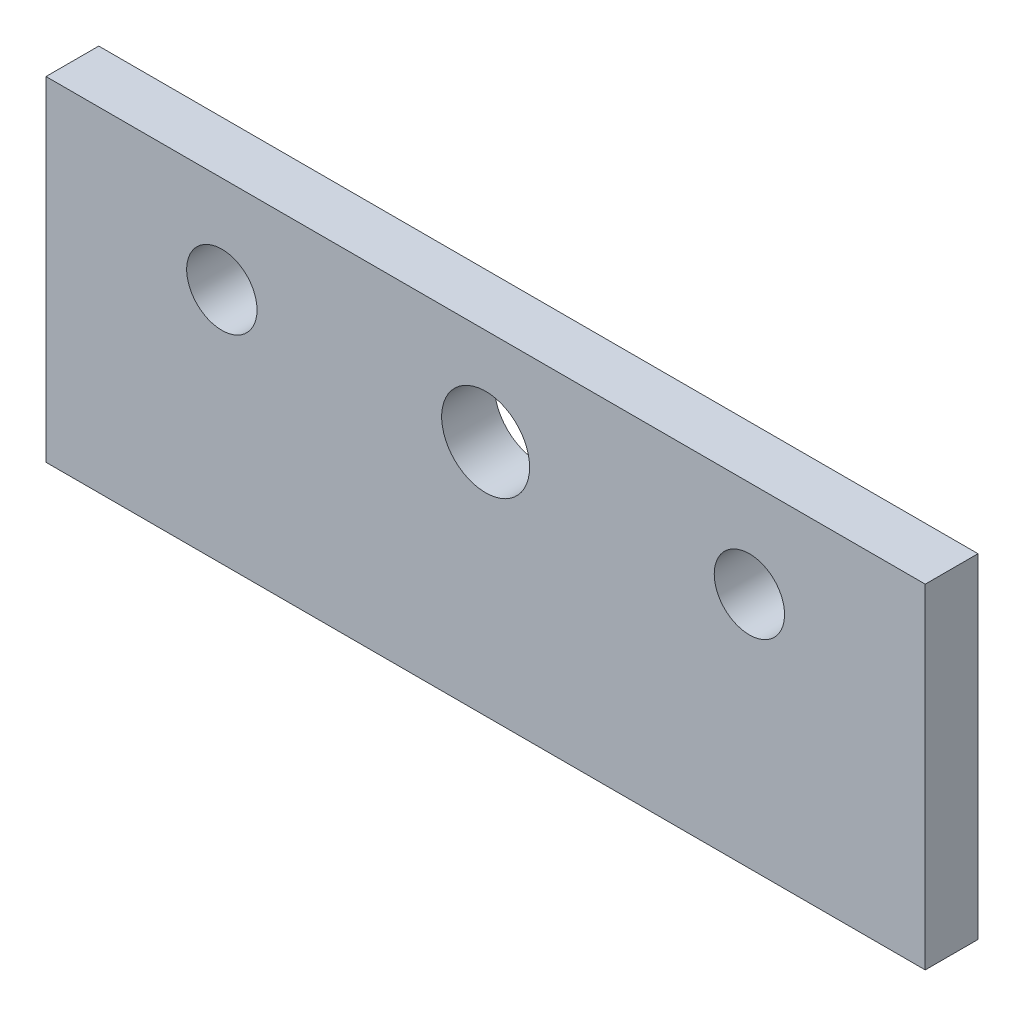
SolidWorks part; units mm, degrees
ref_plane "前视" through (0, 0, 0) normal (0, 0, 1) x (1, 0, 0)
ref_plane "上视" through (0, 0, 0) normal (0, 1, 0) x (1, 0, 0)
ref_plane "右视" through (0, 0, 0) normal (1, 0, 0) x (0, 0, -1)
sketch "草图1" plane through (0, 0, 0) normal (0, 0, 1) x (1, 0, 0)
  line L0 (-25, 4) -> (25, 4) construction
  line L1 (-25, 9.5) -> (25, 9.5)
  line L2 (-25, 9.5) -> (-25, -9.5)
  line L3 (-25, -9.5) -> (25, -9.5)
  line L4 (25, 9.5) -> (25, -9.5)
  line L5 (-25, 9.5) -> (25, -9.5) construction
  line L6 (-25, -9.5) -> (25, 9.5) construction
  line L7 (0, 0) -> (0, 15.22) construction
  circle A0 centre (-15, 4) radius 2
  circle A1 centre (15, 4) radius 2
  point P0 (0, 0)
  dimension "D4" = 4
  dimension "D1" = 50
  dimension "D2" = 19
  dimension "D3" = 5.5
  dimension "D5" = 30
base flange "基体-法兰1" sketch "草图1" thickness 3 reverse thickness direction no parameters "D1"=0.5
hole_wizard "M6 螺纹孔1" positions "草图8" profile "草图7" tap size "M6" standard "GB" end condition up to next
sketch "草图8" plane through (0, 0, 0) normal (0, 0, 1) x (1, 0, 0)
  line L0 (-15, 4) -> (15, 4) construction
  point P0 (0, 4)
sketch "草图7" plane through (0, 4, 0) normal (1, 0, 0) x (0, -1, 0)
  line L0 (0, 0) -> (0, 3)
  line L1 (0, 3) -> (2.5, 3)
  line L2 (2.5, 3) -> (2.5, 0)
  line L5 (2.5, 0) -> (0, 0)
  line L11 (0, -6.35) -> (0, 107.95) construction
  dimension "通孔螺纹孔钻头直径" = 5
  dimension "通孔螺纹孔钻头深度" = 3
cosmetic thread "孔螺蚊线1"
sketch "折弯-线1" plane through (0, 0, 0) normal (0, 1, 0) x (1, 0, 0)
sketch "边界框1" plane through (0, 0, 0) normal (0, 1, 0) x (1, 0, 0)
sheet metal parameters "钣金1" thickness 3 parameters "D1"=0.5
flat pattern "平板型式1" [suppressed]
sketch "折弯-线2" plane through (0, 0, 0) normal (0, 1, 0) x (1, 0, 0)
sketch "边界框2" [suppressed] plane through (0, 0, 0) normal (0, 1, 0) x (1, 0, 0)
sheet metal parameters "钣金2" thickness 3 parameters "D1"=0.5
flat pattern "平板型式1"
sketch "折弯-线2" plane through (0, 0, 0) normal (0, 1, 0) x (1, 0, 0)
sketch "边界框2" [suppressed] plane through (0, 0, 0) normal (0, 1, 0) x (1, 0, 0)
